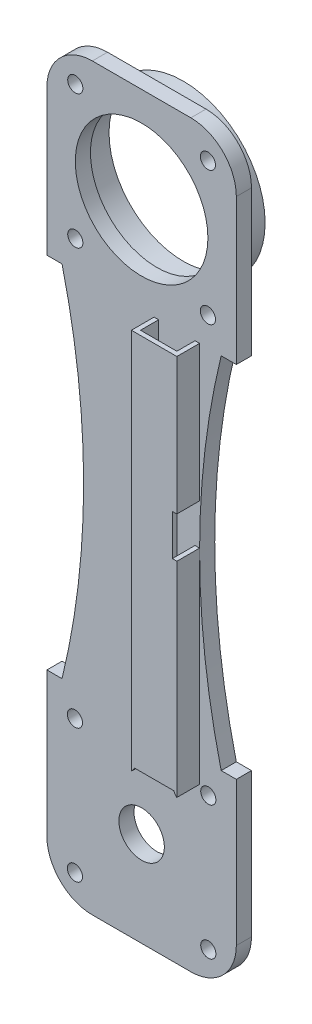
SolidWorks part; units mm, degrees
ref_plane "Front Plane" through (0, 0, 0) normal (0, 0, 1) x (1, 0, 0)
ref_plane "Top Plane" through (0, 0, 0) normal (0, 1, 0) x (1, 0, 0)
ref_plane "Right Plane" through (0, 0, 0) normal (1, 0, 0) x (0, 0, -1)
sketch "Sketch1" plane through (0, 0, 0) normal (0, 0, 1) x (1, 0, 0)
  line L0 (-13.335, -76.2) -> (-15.875, -76.2)
  line L1 (15.875, -16.002) -> (13.335, -16.002)
  line L2 (15.875, -16.002) -> (15.875, 8.382)
  line L3 (8.255, 16.002) -> (-8.255, 16.002)
  line L4 (-15.875, -16.002) -> (-15.875, 8.382)
  line L5 (15.875, -16.002) -> (-15.875, 16.002) construction
  line L6 (15.875, 16.002) -> (-15.875, -16.002) construction
  line L7 (8.255, -107.95) -> (-8.255, -107.95)
  line L8 (15.875, -100.33) -> (15.875, -76.2)
  line L9 (15.875, -76.2) -> (13.335, -76.2)
  line L10 (-15.875, -100.33) -> (-15.875, -76.2)
  line L11 (15.875, -107.95) -> (-15.875, -76.2) construction
  line L12 (15.875, -76.2) -> (-15.875, -107.95) construction
  line L13 (11.1125, -11.2014) -> (-11.1125, -11.2014) construction
  line L14 (11.1125, -11.2014) -> (11.1125, 11.2014) construction
  line L15 (11.1125, 11.2014) -> (-11.1125, 11.2014) construction
  line L16 (-11.1125, -11.2014) -> (-11.1125, 11.2014) construction
  line L17 (11.1125, -11.2014) -> (-11.1125, 11.2014) construction
  line L18 (11.1125, 11.2014) -> (-11.1125, -11.2014) construction
  line L19 (-13.335, -16.002) -> (-15.875, -16.002)
  circle A0 centre (0, 0) radius 11.1125
  arc A1 (15.875, 8.382) -> (8.255, 16.002) centre (8.255, 8.382) ccw
  arc A2 (-15.875, 8.382) -> (-8.255, 16.002) centre (-8.255, 8.382) cw
  arc A3 (-13.335, -16.002) -> (-13.335, -76.2) centre (-136.7167, -46.101) cw
  arc A4 (13.335, -16.002) -> (13.335, -76.2) centre (136.7167, -46.101) ccw
  circle A5 centre (11.1125, 11.2014) radius 1.27
  circle A6 centre (11.1125, -11.2014) radius 1.27
  circle A7 centre (-11.1125, -11.2014) radius 1.27
  circle A8 centre (-11.1125, 11.2014) radius 1.27
  arc A9 (15.875, -100.33) -> (8.255, -107.95) centre (8.255, -100.33) cw
  arc A10 (-8.255, -107.95) -> (-15.875, -100.33) centre (-8.255, -100.33) cw
  point P0 (0, 0)
  point P20 (0, -92.075)
  dimension "D3" = 22.225
  dimension "D4" = 7.62
  dimension "D7" = 127
  dimension "D10" = 2.54
  dimension "D11" = 7.62
  dimension "D1" = 31.75
  dimension "D2" = 32.004
  dimension "D5" = 2.54
  dimension "D6" = 2.54
  dimension "D8" = 76.2
  dimension "D9" = 31.75
extrude "Boss-Extrude1" add sketch "Sketch1" along normal blind 2.54
sketch "Sketch2" plane through (0, 0, 0) normal (0, 0, -1) x (-1, 0, 0)
  line L0 (-15.875, -76.2) -> (15.875, -107.95) construction
  line L1 (11.176, -103.251) -> (-11.176, -103.251) construction
  line L2 (11.176, -103.251) -> (11.176, -80.899) construction
  line L3 (11.176, -80.899) -> (-11.176, -80.899) construction
  line L4 (-11.176, -103.251) -> (-11.176, -80.899) construction
  line L5 (11.176, -103.251) -> (-11.176, -80.899) construction
  line L6 (11.176, -80.899) -> (-11.176, -103.251) construction
  circle A0 centre (-11.176, -80.899) radius 1.27
  circle A1 centre (11.176, -80.899) radius 1.27
  circle A2 centre (11.176, -103.251) radius 1.27
  circle A3 centre (-11.176, -103.251) radius 1.27
  circle A5 centre (0, -92.075) radius 3.81
  point P0 (0, -92.075)
  dimension "D2" = 2.54
  dimension "D3" = 7.62
  dimension "D1" = 22.352
extrude "Cut-Extrude1" cut sketch "Sketch2" against normal blind 2.54
sketch "Sketch3" plane through (0, 0, 0) normal (0, 0, -1) x (-1, 0, 0)
  circle A0 centre (0, 0) radius 12.446
  circle A1 centre (0, 0) radius 13.716
  dimension "D1" = 24.892
  dimension "D2" = 27.432
extrude "Boss-Extrude2" add sketch "Sketch3" along normal blind 4.445
sketch "Sketch4" plane through (0, 0, 2.54) normal (0, 0, 1) x (1, 0, 0)
  line L0 (15.875, -76.2) -> (13.335, -76.2) construction
  line L1 (2.0967, -16.002) -> (9.7167, -16.002)
  line L2 (2.0967, -16.002) -> (2.0967, -80.01)
  line L3 (2.0967, -80.01) -> (9.7167, -80.01)
  line L4 (9.7167, -16.002) -> (9.7167, -80.01)
  arc A0 (13.335, -16.002) -> (13.335, -76.2) centre (136.7167, -46.101) ccw construction
  dimension "D1" = 7.62
  dimension "D2" = 3.81
extrude "Extrude-Thin1" add sketch "Sketch4" along normal blind 3.81 thin
sketch "Sketch5" plane through (0, -80.01, 0) normal (0, -1, 0) x (1, 0, 0)
  line L0 (2.0967, 6.35) -> (9.7167, 6.35) construction
  line L1 (2.8587, 6.35) -> (8.9547, 6.35)
  line L2 (2.8587, 6.35) -> (2.8587, 2.54)
  line L3 (2.8587, 2.54) -> (8.9547, 2.54)
  line L4 (8.9547, 6.35) -> (8.9547, 2.54)
  line L5 (15.875, 2.54) -> (8.255, 2.54) construction
  line L6 (2.0967, 6.35) -> (2.0967, 2.54) construction
  line L7 (9.7167, 6.35) -> (9.7167, 2.54) construction
  dimension "D1" = 0.762
  dimension "D2" = 0.762
extrude "Cut-Extrude2" cut sketch "Sketch5" against normal blind 76.2
sketch "Sketch6" plane through (0, 0, 6.35) normal (0, 0, 1) x (1, 0, 0)
  line L1 (2.0967, -16.002) -> (9.7167, -16.002)
  line L2 (2.0967, -16.002) -> (2.0967, -80.01)
  line L3 (2.0967, -80.01) -> (9.7167, -80.01)
  line L4 (9.7167, -16.002) -> (9.7167, -80.01)
extrude "Boss-Extrude3" add sketch "Sketch6" against normal blind 0.762
fillet "Fillet1" radius 2.54 3 edges at (8.9547, -80.01, 4.064) (5.9067, -80.01, 5.588) (2.8587, -80.01, 4.064)
sketch "Sketch7" plane through (9.7167, 0, 0) normal (1, 0, 0) x (0, 0, -1)
  line L0 (-6.35, -80.01) -> (-6.35, -16.002) construction
  line L1 (-6.35, -38.862) -> (-2.54, -38.862)
  line L2 (-6.35, -38.862) -> (-6.35, -45.72)
  line L3 (-6.35, -45.72) -> (-2.54, -45.72)
  line L4 (-2.54, -38.862) -> (-2.54, -45.72)
  line L5 (-2.54, -16.002) -> (-2.54, -46.101) construction
  line L6 (-6.35, -16.002) -> (-2.54, -16.002) construction
  line L7 (-6.35, -80.01) -> (-2.54, -80.01) construction
  dimension "D1" = 22.86
  dimension "D2" = 34.29
extrude "Cut-Extrude3" cut sketch "Sketch7" against normal blind 0.762
